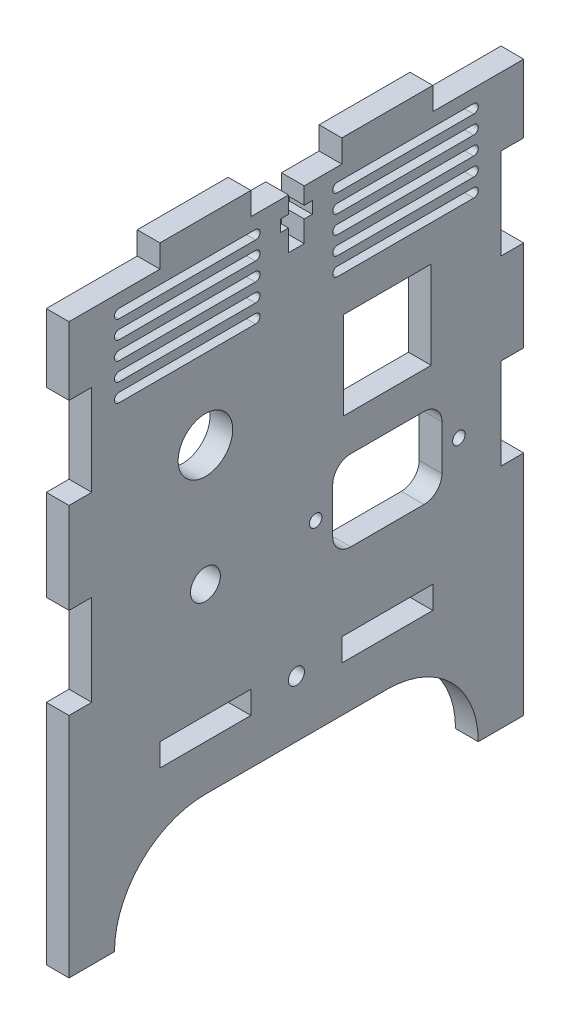
SolidWorks part; units mm, degrees
ref_plane "Front Plane" through (0, 0, 0) normal (0, 0, 1) x (1, 0, 0)
ref_plane "Top Plane" through (0, 0, 0) normal (0, 1, 0) x (1, 0, 0)
ref_plane "Right Plane" through (0, 0, 0) normal (1, 0, 0) x (0, 0, -1)
sketch "Sketch1" plane through (0, 0, 0) normal (1, 0, 0) x (0, 0, -1)
  line L1 (-63.5, 82.55) -> (63.5, 82.55)
  line L2 (-63.5, 82.55) -> (-63.5, -82.55)
  line L3 (-63.5, -82.55) -> (63.5, -82.55)
  line L4 (63.5, 82.55) -> (63.5, -82.55)
  line L5 (-63.5, 82.55) -> (63.5, -82.55) construction
  line L6 (-63.5, -82.55) -> (63.5, 82.55) construction
  point P0 (0, 0)
  dimension "D1" = 127
  dimension "D2" = 165.1
extrude "Boss-Extrude1" add sketch "Sketch1" along normal blind 6.35
sketch "Sketch2" plane through (6.35, 0, 0) normal (1, 0, 0) x (0, 0, -1)
  line L1 (-63.5, 82.55) -> (-38.1, 82.55)
  line L2 (-63.5, 82.55) -> (-63.5, 76.2)
  line L3 (-63.5, 76.2) -> (-38.1, 76.2)
  line L4 (-38.1, 82.55) -> (-38.1, 76.2)
  dimension "D1" = 25.4
  dimension "D2" = 6.35
extrude "Cut-Extrude1" cut sketch "Sketch2" against normal blind 6.35
pattern_linear "LPattern1" count 3 spacing 50.8 along (0, 0, -1) of "Cut-Extrude1"
sketch "Sketch5" plane through (6.35, 0, 0) normal (1, 0, 0) x (0, 0, -1)
  line L0 (-25.4, -82.55) -> (25.4, -82.55) construction
  line L1 (-63.5, -82.55) -> (63.5, -82.55) construction
  line L2 (-25.4, -57.15) -> (25.4, -57.15)
  line L3 (-25.4, -107.95) -> (25.4, -107.95)
  arc A0 (-25.4, -57.15) -> (-25.4, -107.95) centre (-25.4, -82.55) ccw
  arc A1 (25.4, -107.95) -> (25.4, -57.15) centre (25.4, -82.55) ccw
  point P4 (0, -82.55)
  dimension "D2" = 25.4
  dimension "D1" = 50.8
extrude "Cut-Extrude4" cut sketch "Sketch5" against normal blind 6.35
sketch "Sketch8" plane through (6.35, 0, 0) normal (1, 0, 0) x (0, 0, -1)
  line L0 (63.5, -82.55) -> (63.5, 76.2) construction
  line L1 (63.5, 57.15) -> (57.15, 57.15)
  line L2 (63.5, 57.15) -> (63.5, 31.75)
  line L3 (63.5, 31.75) -> (57.15, 31.75)
  line L4 (57.15, 57.15) -> (57.15, 31.75)
  line L5 (38.1, 82.55) -> (12.7, 82.55) construction
  dimension "D1" = 25.4
  dimension "D2" = 25.4
  dimension "D3" = 6.35
extrude "Cut-Extrude6" cut sketch "Sketch8" against normal blind 6.35
pattern_linear "LPattern4" count 2 spacing 50.8 along (0, -1, 0) of "Cut-Extrude6"
ref_plane "Plane1" through (0, 0, 0) normal (0, 0, 1) x (1, 0, 0)
mirror "Mirror1" about plane through (0, 0, 0) normal (0, 0, 1) of "LPattern4"
sketch "Sketch9" plane through (0, 0, 0) normal (-1, 0, 0) x (0, 0, 1)
  line L0 (-63.5, -82.55) -> (-63.5, -19.05) construction
  line L1 (-38.1, -38.1) -> (-12.7, -38.1)
  line L2 (-38.1, -38.1) -> (-38.1, -44.45)
  line L3 (-38.1, -44.45) -> (-12.7, -44.45)
  line L4 (-12.7, -38.1) -> (-12.7, -44.45)
  line L5 (-38.1, 82.55) -> (-12.7, 82.55) construction
  point P6 (-25.4, 82.55)
  dimension "D1" = 25.4
  dimension "D2" = 6.35
  dimension "D3" = 25.4
  dimension "D4" = 120.65
extrude "Cut-Extrude7" cut sketch "Sketch9" against normal blind 6.35
pattern_linear "LPattern6" count 2 spacing 50.8 along (0, 0, 1) of "Cut-Extrude7"
sketch "Sketch16" plane through (0, 0, 0) normal (-1, 0, 0) x (0, 0, 1)
  line L0 (12.7, 76.2) -> (-12.7, 76.2) construction
  line L1 (-2.1971, 76.2) -> (2.1971, 76.2)
  line L2 (-2.1971, 76.2) -> (-2.1971, 62.23)
  line L3 (-2.1971, 62.23) -> (2.1971, 62.23)
  line L4 (2.1971, 76.2) -> (2.1971, 62.23)
  line L5 (-12.7, 76.2) -> (-12.7, 82.55) construction
  line L7 (-4.445, 71.501) -> (4.445, 71.501)
  line L8 (-4.445, 71.501) -> (-4.445, 68.199)
  line L9 (-4.445, 68.199) -> (4.445, 68.199)
  line L10 (4.445, 71.501) -> (4.445, 68.199)
  point P6 (0, 62.23)
  point P13 (0, 71.501)
  point P14 (4.445, 69.85)
  dimension "D1" = 4.3942
  dimension "D2" = 13.97
  dimension "D3" = 12.7
  dimension "D4" = 3.302
  dimension "D5" = 8.89
  dimension "D6" = 12.7
  dimension "D7" = 6.35
extrude "Cut-Extrude14" cut sketch "Sketch16" against normal blind 6.35 contours L7 L10 L9 L8 | L1 L4 L3 L2
hole_wizard "#8 Clearance Hole1" positions "Sketch18" profile "Sketch17" hole size "#8" standard "ANSI Inch"
sketch "Sketch18" plane through (0, 0, 0) normal (-1, 0, 0) x (0, 0, 1)
  line L3 (-12.7, -44.45) -> (-12.7, -38.1) construction
  line L4 (38.1, -38.1) -> (12.7, -38.1) construction
  point P0 (0, -41.275)
  point P16 (-12.7, -41.275)
  dimension "D1" = 12.7
  dimension "D2" = 3.175
sketch "Sketch17" plane through (0, -41.275, 0) normal (0, 1, 0) x (0, 0, 1)
  line L0 (0, 0) -> (0, 11.5107)
  line L1 (0, 11.5107) -> (2.2479, 10.16)
  line L2 (2.2479, 10.16) -> (2.2479, 0)
  line L5 (2.2479, 0) -> (0, 0)
  line L10 (0, 11.5107) -> (-2.2479, 10.16) construction
  line L11 (0, -6.35) -> (0, 107.95) construction
  dimension "Hole Dia." = 4.4958
  dimension "Hole Depth" = 10.16
  dimension "Drill Angle" = 118
sketch "Sketch19" plane through (0, 0, 0) normal (-1, 0, 0) x (0, 0, 1)
  line L0 (-49.53, 71.1789) -> (-11.43, 71.1789) construction
  line L1 (-49.53, 72.4489) -> (-11.43, 72.4489)
  line L2 (-49.53, 69.9089) -> (-11.43, 69.9089)
  line L3 (-38.1, 82.55) -> (-38.1, 76.2) construction
  arc A0 (-49.53, 72.4489) -> (-49.53, 69.9089) centre (-49.53, 71.1789) ccw
  arc A1 (-11.43, 69.9089) -> (-11.43, 72.4489) centre (-11.43, 71.1789) ccw
  point P2 (-30.48, 71.1789)
  point P7 (-30.48, 72.4489)
  dimension "D2" = 1.27
  dimension "D1" = 38.1
  dimension "D3" = 7.62
extrude "Cut-Extrude15" cut sketch "Sketch19" against normal blind 6.35
mirror "Mirror2" about plane through (0, 0, 0) normal (0, 0, 1) of "Cut-Extrude15"
pattern_linear "LPattern7" count 5 spacing 5.08 along (0, -1, 0) of "Mirror2"
sketch "Sketch20" plane through (0, 0, 0) normal (-1, 0, 0) x (0, 0, 1)
  line L1 (-35.65, 4.9) -> (-15.15, 4.9)
  line L2 (-40.65, -0.1) -> (-40.65, -12.6)
  line L3 (-35.65, -17.6) -> (-15.15, -17.6)
  line L4 (-10.15, -0.1) -> (-10.15, -12.6)
  line L5 (-63.5, 6.35) -> (-63.5, 31.75) construction
  circle A0 centre (-45.4, -6.35) radius 1.75
  circle A1 centre (-5.4, -6.35) radius 1.75
  arc A2 (-40.65, -12.6) -> (-35.65, -17.6) centre (-35.65, -12.6) ccw
  arc A3 (-15.15, 4.9) -> (-10.15, -0.1) centre (-15.15, -0.1) cw
  arc A4 (-15.15, -17.6) -> (-10.15, -12.6) centre (-15.15, -12.6) ccw
  arc A5 (-40.65, -0.1) -> (-35.65, 4.9) centre (-35.65, -0.1) cw
  point P8 (-25.4, 4.9)
  point P13 (-40.65, -6.35)
  point P18 (-10.15, 4.9)
  point P21 (-10.15, -17.6)
  point P24 (-40.65, 4.9)
  dimension "D1" = 3.5
  dimension "D2" = 3.5
  dimension "D10" = 5
  dimension "D11" = 5
  dimension "D12" = 5
  dimension "D13" = 5
  dimension "D3" = 40
  dimension "D4" = 30.5
  dimension "D5" = 22.5
  dimension "D6" = 38.1
extrude "Cut-Extrude16" cut sketch "Sketch20" against normal blind 7.62
sketch "Sketch22" plane through (0, 0, 0) normal (-1, 0, 0) x (0, 0, 1)
  line L0 (-15.15, 4.9) -> (-35.65, 4.9) construction
  line L1 (-37.65, 39.56) -> (-13.15, 39.56)
  line L2 (-37.65, 39.56) -> (-37.65, 15.06)
  line L3 (-37.65, 15.06) -> (-13.15, 15.06)
  line L4 (-13.15, 39.56) -> (-13.15, 15.06)
  point P4 (-25.4, 15.06)
  point P5 (-25.4, 4.9)
  dimension "D1" = 24.5
  dimension "D2" = 24.5
  dimension "D3" = 0
  dimension "D4" = 10.16
extrude "Cut-Extrude17" cut sketch "Sketch22" against normal blind 6.35
sketch "Sketch23" plane through (0, 0, 0) normal (-1, 0, 0) x (0, 0, 1)
  line L0 (-13.15, 15.06) -> (-13.15, 39.56) construction
  line L2 (63.5, 31.75) -> (63.5, 6.35) construction
  circle A0 centre (25.4, 27.31) radius 7.62
  point P2 (-13.15, 27.31)
  dimension "D1" = 15.24
  dimension "D2" = 0
  dimension "D3" = 38.1
extrude "Cut-Extrude18" cut sketch "Sketch23" against normal blind 7.62
sketch "Sketch24" plane through (0, 0, 0) normal (-1, 0, 0) x (0, 0, 1)
  line L1 (57.15, 6.35) -> (57.15, -19.05) construction
  circle A0 centre (25.4, -6.35) radius 4.1672
  circle A1 centre (25.4, 27.31) radius 7.62 construction
  point P4 (57.15, -6.35)
  dimension "D1" = 0
  dimension "D2" = 8.3344
  dimension "D3" = 0
extrude "Cut-Extrude19" cut sketch "Sketch24" against normal blind 7.62
